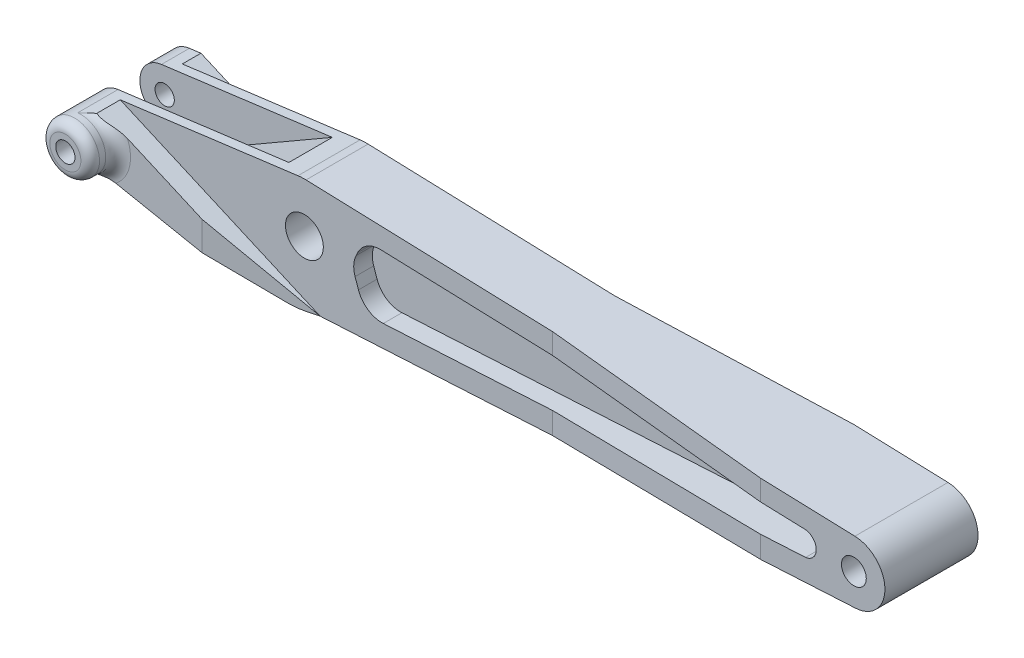
SolidWorks part; units mm, degrees
material "ABS"
ref_plane "Front Plane" through (0, 0, 0) normal (0, 0, 1) x (1, 0, 0)
ref_plane "Top Plane" through (0, 0, 0) normal (0, 1, 0) x (1, 0, 0)
ref_plane "Right Plane" through (0, 0, 0) normal (1, 0, 0) x (0, 0, -1)
sketch "layout" plane through (0, 0, 0) normal (0, 0, 1) x (1, 0, 0)
  line L0 (-107.873, 0) -> (194.2258, 0) construction
  line L1 (0, 80.6323) -> (0, -88.5321) construction
  line L2 (-31.5161, 3.9666) -> (-1.0323, 7.9331)
  line L3 (0.2637, 7.9957) -> (91.1648, 4.9973)
  line L4 (91.2747, -4.9924) -> (0.5495, -9.9849)
  line L5 (-1.9355, -9.8109) -> (-31.7742, -3.9244)
  circle A0 centre (0, 0) radius 3
  circle A1 centre (-31, 0) radius 1.5
  circle A2 centre (91, 0) radius 3
  arc A3 (-31.5161, 3.9666) -> (-31.7742, -3.9244) centre (-31, 0) ccw
  arc A4 (-1.9355, -9.8109) -> (0.5495, -9.9849) centre (0, 0) ccw
  arc A5 (91.2747, -4.9924) -> (91.1648, 4.9973) centre (91, 0) ccw
  arc A7 (-1.0323, 7.9331) -> (0.2637, 7.9957) centre (0, 0) cw
  dimension "D1" = 10
  dimension "D2" = 6
  dimension "D3" = 5
  dimension "D4" = 91
  dimension "D5" = 31
  dimension "D6" = 3
  dimension "D7" = 6
  dimension "D8" = 4
  dimension "D9" = 8
sketch "Sketch2" plane through (0, 0, 0) normal (0, 0, 1) x (1, 0, 0)
  line L0 (0.2637, 7.9957) -> (91.1648, 4.9973) construction
  line L1 (91.2747, -4.9924) -> (0.5495, -9.9849) construction
  line L2 (-1.9355, -9.8109) -> (-31.7742, -3.9244) construction
  line L3 (-31.5161, 3.9666) -> (-1.0323, 7.9331) construction
  line L4 (0.2637, 7.9957) -> (91.1648, 4.9973)
  line L5 (91.2747, -4.9924) -> (0.5495, -9.9849)
  line L6 (-1.9355, -9.8109) -> (-31.7742, -3.9244)
  line L7 (-31.5161, 3.9666) -> (-1.0323, 7.9331)
  arc A0 (91.2747, -4.9924) -> (91.1648, 4.9973) centre (91, 0) ccw construction
  arc A1 (-1.9355, -9.8109) -> (0.5495, -9.9849) centre (0, 0) ccw construction
  arc A2 (-31.5161, 3.9666) -> (-31.7742, -3.9244) centre (-31, 0) ccw construction
  arc A4 (91.2747, -4.9924) -> (91.1648, 4.9973) centre (91, 0) ccw
  arc A5 (-1.9355, -9.8109) -> (0.5495, -9.9849) centre (0, 0) ccw
  arc A6 (-31.5161, 3.9666) -> (-31.7742, -3.9244) centre (-31, 0) ccw
  arc A7 (0.2637, 7.9957) -> (-1.0323, 7.9331) centre (0, 0) ccw
extrude "Boss-Extrude1" add sketch "Sketch2" along normal mid plane 15
sketch "Sketch3" plane through (0, 0, 0) normal (0, 0, 1) x (1, 0, 0)
  circle A0 centre (0, 0) radius 2
  dimension "D1" = 4
extrude "Cut-Extrude1" cut sketch "Sketch3" against normal through all both and the other way through all
sketch "Sketch5" plane through (0, 0, 0) normal (0, 0, 1) x (1, 0, 0)
  circle A0 centre (91, 0) radius 2
  dimension "D1" = 4
extrude "Cut-Extrude3" cut sketch "Sketch5" against normal through all both and the other way through all
sketch "Sketch8" plane through (0, 0, 0) normal (0, 0, 1) x (1, 0, 0)
  line L2 (-25.8822, -5.0867) -> (-4, 7.547)
  line L3 (-1.9355, -9.8109) -> (-31.7742, -3.9244) construction
  line L4 (91.1648, 4.9973) -> (0.2637, 7.9957)
  line L5 (0.5495, -9.9849) -> (91.2747, -4.9924)
  line L6 (-31.7742, -3.9244) -> (-1.9355, -9.8109)
  line L7 (-1.0323, 7.9331) -> (-31.5161, 3.9666)
  line L10 (-31.7742, -3.9244) -> (-4, -9.4036)
  line L11 (-4, 7.547) -> (-31.5161, 3.9666)
  line L12 (-4, 7.547) -> (-4, -9.4036) construction
  arc A7 (0.2637, 7.9957) -> (-1.0323, 7.9331) centre (0, 0) ccw
  arc A10 (91.2747, -4.9924) -> (91.1648, 4.9973) centre (91, 0) ccw
  arc A11 (-1.9355, -9.8109) -> (0.5495, -9.9849) centre (0, 0) ccw
  arc A12 (-31.5161, 3.9666) -> (-31.7742, -3.9244) centre (-31, 0) ccw
  arc A16 (-31.5161, 3.9666) -> (-31.7742, -3.9244) centre (-31, 0) ccw
  dimension "D1" = 60
  dimension "D2" = 4
  dimension "D4" = 0
extrude "Cut-Extrude4" cut sketch "Sketch8" against normal mid plane 7 contours L11 A16 L10 L2 region at (-23.0959, 1.4067, 0)
sketch "Sketch9" plane through (0, 0, 0) normal (0, 1, 0) x (1, 0, 0)
  line L0 (105.9892, 0) -> (-59.2384, 0) construction
  line L1 (76, 7.5) -> (40, 5)
  line L2 (91.1648, 7.5) -> (0.2637, 7.5) construction
  line L3 (40, 5) -> (-35, 5)
  line L4 (-35, 7.5) -> (-35, 3.5) construction
  line L5 (-35, 5) -> (-35, 7.5)
  line L6 (-35, 7.5) -> (76, 7.5)
  line L7 (0, 26.3779) -> (0, -48.7291) construction
  line L8 (-35, -7.5) -> (-35, -5)
  line L9 (-35, -3.5) -> (-35, -7.5) construction
  line L10 (-35, -5) -> (40, -5)
  line L11 (40, -5) -> (76, -7.5)
  line L12 (91.1648, -7.5) -> (0.2637, -7.5) construction
  line L13 (76, -7.5) -> (-35, -7.5)
  line L14 (76, 7.5) -> (76, -7.5) construction
  line L15 (40, 5) -> (40, -5) construction
  dimension "D1" = 5
  dimension "D2" = 76
  dimension "D3" = 40
  dimension "D4" = 5
extrude "Cut-Extrude5" cut sketch "Sketch9" against normal through all both and the other way through all
sketch "Sketch4" plane through (0, 0, 0) normal (0, 0, 1) x (1, 0, 0)
  circle A0 centre (0, 0) radius 3.05
  dimension "D1" = 6.1
extrude "Cut-Extrude2" cut sketch "Sketch4" against normal blind 2.6 from surface starting at face at (-2, 0, 5)
sketch "Sketch6" plane through (0, 0, 5) normal (0, 0, 1) x (1, 0, 0)
  line L0 (-29.6594, 4.2082) -> (2.5394, -9.8754)
  line L1 (40, -7.814) -> (0.5495, -9.9849) construction
  line L2 (-31.5161, 3.9666) -> (-1.0323, 7.9331) construction
  line L3 (-1.9355, -9.8109) -> (-31.7742, -3.9244) construction
  line L4 (-31.5161, 3.9666) -> (-29.6594, 4.2082)
  line L5 (2.5394, -9.8754) -> (0.5495, -9.9849)
  line L6 (-1.9355, -9.8109) -> (-31.7742, -3.9244)
  circle A0 centre (-31, 0) radius 5 construction
  arc A1 (-31.5161, 3.9666) -> (-31.7742, -3.9244) centre (-31, 0) ccw construction
  arc A2 (-1.9355, -9.8109) -> (0.5495, -9.9849) centre (0, 0) ccw construction
  arc A3 (-31.5161, 3.9666) -> (-31.7742, -3.9244) centre (-31, 0) ccw
  arc A4 (-1.9355, -9.8109) -> (0.5495, -9.9849) centre (0, 0) ccw
  circle A5 centre (0, 0) radius 7.5 construction
  dimension "D2" = 10
  dimension "D1" = 15
extrude "Boss-Extrude2" add sketch "Sketch6" along normal blind 3
sketch "Sketch14" plane through (0, 0, 0) normal (0, 1, 0) x (1, 0, 0)
  line L0 (2.5394, -5) -> (2.5394, -8)
  line L1 (2.5394, -8) -> (-13.4606, -8)
  line L2 (2.5394, -8) -> (-29.6594, -8) construction
  line L3 (-13.4606, -8) -> (2.5394, -5)
  dimension "D1" = 16
extrude "Cut-Extrude9" cut sketch "Sketch14" against normal through all both and the other way through all
sketch "Sketch10" plane through (0, 0, 5) normal (0, 0, 1) x (1, 0, 0)
  line L0 (-51.3422, 0) -> (118.5827, 0) construction
  line L1 (7.627, 0) -> (9.6935, 4.3624)
  line L2 (9.6935, 4.3624) -> (83.0641, 1.9423)
  line L3 (83.227, -1.93) -> (9.6935, -5.9764)
  line L4 (9.6935, -5.9764) -> (7.627, 0)
  line L6 (40, 6.685) -> (76, 5.4975) construction
  line L7 (0.2637, 7.9957) -> (40, 6.685) construction
  line L8 (40, -7.814) -> (2.5394, -9.8754) construction
  arc A1 (83.227, -1.93) -> (83.0641, 1.9423) centre (83, 0) ccw
  circle A2 centre (91, 0) radius 2 construction
  dimension "D3" = 8
  dimension "D1" = 3.3204
  dimension "D2" = 3.5
extrude "Cut-Extrude6" cut sketch "Sketch10" against normal offset from surface 2 and the other way through all up to plane "Front Plane"
fillet "Fillet3" radius 4 3 edges at (9.6935, -5.9764, 3.5) (9.6935, 4.3624, 3.5) (7.627, 0, 3.5)
mirror "Mirror1" about plane through (0, 0, 0) normal (0, 0, 1) of "Cut-Extrude9", "Fillet3", "Cut-Extrude6", "Boss-Extrude2"
sketch "Sketch11" plane through (0, 0, 0) normal (0, 0, 1) x (1, 0, 0)
  circle A0 centre (-31, 0) radius 1.55
  dimension "D1" = 3.1
extrude "Cut-Extrude7" cut sketch "Sketch11" against normal through all both and the other way through all
extrude "Cut-Extrude8" cut sketch "Sketch4<2>" along normal through all from surface starting at face at (2, 0, -5)
sketch "Sketch4<2>" plane through (0, 0, 0) normal (0, 0, 1) x (1, 0, 0) same geometry as "Sketch4"
sketch "Sketch13" plane through (0, 0, 8) normal (0, 0, 1) x (1, 0, 0)
  circle A1 centre (-31, 0) radius 4
  circle A4 centre (-31, 0) radius 1.55 construction
  circle A5 centre (-31, 0) radius 1.55
extrude "Boss-Extrude3" add sketch "Sketch13" along normal blind 4.5
fillet "Fillet7" radius 2 1 edges at (-27.0021, -0.1307, 8)
fillet "Fillet8" radius 1.5 1 edges at (-27, 0, 12.5)
